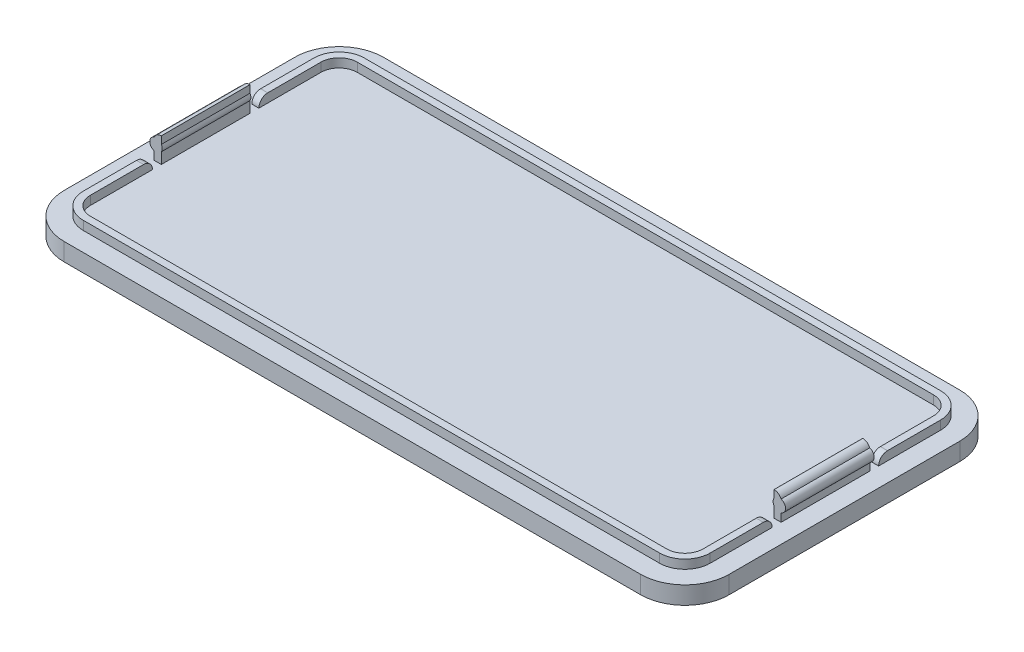
SolidWorks part; units mm, degrees
ref_plane "前视基准面" through (0, 0, 0) normal (0, 0, 1) x (1, 0, 0)
ref_plane "上视基准面" through (0, 0, 0) normal (0, 1, 0) x (1, 0, 0)
ref_plane "右视基准面" through (0, 0, 0) normal (1, 0, 0) x (0, 0, -1)
sketch "zero" plane through (0, 0, 0) normal (0, 1, 0) x (1, 0, 0)
  line L1 (-29.5, 15) -> (29.5, 15)
  line L2 (-32.5, 12) -> (-32.5, -12)
  line L3 (-29.5, -15) -> (29.5, -15)
  line L4 (32.5, 12) -> (32.5, -12)
  line L5 (-32.5, 15) -> (32.5, -15) construction
  line L6 (-32.5, -15) -> (32.5, 15) construction
  line L7 (-25.7, -15) -> (-14.5, -15)
  line L8 (-25.7, -15) -> (-25.7, -9.6569)
  line L9 (-25.7, -9.6569) -> (-14.5, -9.6569)
  line L10 (-14.5, -15) -> (-14.5, -9.6569)
  line L11 (5.2, -15) -> (12.7, -15)
  line L12 (5.2, -15) -> (5.2, -11)
  line L13 (5.2, -11) -> (12.7, -11)
  line L14 (12.7, -15) -> (12.7, -11)
  line L15 (17.8, -15) -> (25.3, -15)
  line L16 (17.8, -15) -> (17.8, -11)
  line L17 (17.8, -11) -> (25.3, -11)
  line L18 (25.3, -15) -> (25.3, -11)
  line L19 (-32.5, 7.7) -> (-19.5, 7.7)
  line L20 (-32.5, 7.7) -> (-32.5, -4.3)
  line L21 (-32.5, -4.3) -> (-19.5, -4.3)
  line L22 (-19.5, 7.7) -> (-19.5, -4.3)
  line L23 (-25.5, 14) -> (25.5, 14)
  line L24 (-25.5, 14) -> (-25.5, 8.8)
  line L25 (-25.5, 8.8) -> (25.5, 8.8)
  line L26 (25.5, 14) -> (25.5, 8.8)
  line L27 (-19.5, 7.2329) -> (-35.5, 7.2329)
  line L28 (-19.5, 7.2329) -> (-19.5, -3.7671)
  line L29 (-19.5, -3.7671) -> (-35.5, -3.7671)
  line L30 (-35.5, 7.2329) -> (-35.5, -3.7671)
  arc A0 (29.5, -15) -> (32.5, -12) centre (29.5, -12) ccw
  arc A1 (29.5, 15) -> (32.5, 12) centre (29.5, 12) cw
  arc A2 (-32.5, -12) -> (-29.5, -15) centre (-29.5, -12) ccw
  arc A3 (-29.5, 15) -> (-32.5, 12) centre (-29.5, 12) ccw
  circle A4 centre (-29, 11.4) radius 3
  circle A5 centre (-29, -11.5) radius 3
  circle A6 centre (29, 11.4) radius 3
  circle A7 centre (29, -11.5) radius 3
  circle A8 centre (-29, 11.4) radius 1.375
  circle A9 centre (-29, -11.5) radius 1.375
  circle A10 centre (29, -11.5) radius 1.375
  circle A11 centre (29, 11.4) radius 1.375
  point P0 (0, 0)
  dimension "D3" = 3
  dimension "D4" = 6
  dimension "D9" = 2.75
  dimension "D1" = 65
  dimension "D2" = 30
  dimension "D5" = 3.6
  dimension "D6" = 3.5
  dimension "D7" = 3.5
  dimension "D8" = 3.5
  dimension "D10" = 12
  dimension "D11" = 7.3
  dimension "D12" = 13
  dimension "D13" = 11.2
  dimension "D14" = 6.8
  dimension "D15" = 19.7
  dimension "D16" = 7.5
  dimension "D17" = 7.5
  dimension "D18" = 5.1
  dimension "D19" = 4
  dimension "D20" = 5.2
  dimension "D21" = 7
  dimension "D22" = 7
  dimension "D23" = 1
  dimension "D24" = 11
  dimension "D25" = 16
sketch "sugar" plane through (0, 0, 0) normal (0, 1, 0) x (1, 0, 0)
  line L1 (-29.5, 15) -> (29.5, 15)
  line L2 (-32.5, 12) -> (-32.5, -12)
  line L3 (-29.5, -15) -> (29.5, -15)
  line L4 (32.5, 12) -> (32.5, -12)
  line L5 (-32.5, 15) -> (32.5, -15) construction
  line L6 (-32.5, -15) -> (32.5, 15) construction
  line L7 (23.5, -11.5) -> (19.5, -11.5)
  line L8 (23.5, -11.5) -> (23.5, -13.9082)
  line L9 (23.5, -13.9082) -> (19.5, -13.9082)
  line L10 (19.5, -11.5) -> (19.5, -13.9082)
  line L11 (16, -11.0071) -> (8.5, -11.0071)
  line L12 (16, -11.0071) -> (16, -15)
  line L13 (16, -15) -> (8.5, -15)
  line L14 (8.5, -11.0071) -> (8.5, -15)
  line L15 (20.5, -13.9082) -> (22.5, -13.9082)
  line L16 (20.5, -13.9082) -> (20.5, -14.8173)
  line L17 (20.5, -14.8173) -> (22.5, -14.8173)
  line L18 (22.5, -13.9082) -> (22.5, -14.8173)
  arc A0 (29.5, 15) -> (32.5, 12) centre (29.5, 12) cw
  arc A1 (29.5, -15) -> (32.5, -12) centre (29.5, -12) ccw
  arc A2 (-32.5, -12) -> (-29.5, -15) centre (-29.5, -12) ccw
  arc A3 (-29.5, 15) -> (-32.5, 12) centre (-29.5, 12) ccw
  circle A4 centre (-29, 11.4) radius 3
  circle A5 centre (-29, 11.4) radius 1.375
  circle A6 centre (-29, -11.5) radius 3
  circle A7 centre (-29, -11.5) radius 1.375
  circle A8 centre (29, 11.4) radius 3
  circle A9 centre (29, 11.4) radius 1.375
  circle A10 centre (29, -11.5) radius 3
  circle A11 centre (29, -11.5) radius 1.375
  dimension "D3" = 3
  dimension "D1" = 65
  dimension "D2" = 30
  dimension "D4" = 9
  dimension "D5" = 4
  dimension "D6" = 3.5
  dimension "D7" = 7.5
  dimension "D8" = 2
  dimension "D9" = 1
sketch "case" plane through (0, 0, 0) normal (0, 1, 0) x (1, 0, 0)
  line L1 (-34.0422, 18) -> (30.9578, 18)
  line L2 (-39.0422, 13) -> (-39.0422, -13)
  line L3 (-34.0422, -18) -> (30.9578, -18)
  line L4 (35.9578, 13) -> (35.9578, -13)
  line L5 (-39.0422, 18) -> (35.9578, -18) construction
  line L6 (-39.0422, -18) -> (35.9578, 18) construction
  arc A0 (-39.0422, -13) -> (-34.0422, -18) centre (-34.0422, -13) ccw
  arc A1 (30.9578, -18) -> (35.9578, -13) centre (30.9578, -13) ccw
  arc A2 (30.9578, 18) -> (35.9578, 13) centre (30.9578, 13) cw
  arc A3 (-34.0422, 18) -> (-39.0422, 13) centre (-34.0422, 13) ccw
  point P0 (-1.5422, 0)
  point P3 (-1.5422, 0)
  dimension "D3" = 5
  dimension "D1" = 75
  dimension "D2" = 36
extrude "凸台-拉伸2" add sketch "case" along normal blind 2
sketch "草图2" plane through (0, 0, 0) normal (0, 1, 0) x (1, 0, 0)
  line L4 (-34.0422, -15.05) -> (30.9578, -15.05)
  line L5 (33.0078, -13) -> (33.0078, 13)
  line L6 (30.9578, 15.05) -> (-34.0422, 15.05)
  line L7 (-36.0922, 13) -> (-36.0922, -13)
  line L8 (33.8078, -13) -> (33.8078, 13)
  line L9 (30.9578, 15.85) -> (-34.0422, 15.85)
  line L10 (-36.8922, 13) -> (-36.8922, -13)
  line L11 (-34.0422, -15.85) -> (30.9578, -15.85)
  line L12 (33.8078, -13) -> (33.8078, 13)
  line L13 (30.9578, 15.85) -> (-34.0422, 15.85)
  line L14 (-36.8922, 13) -> (-36.8922, -13)
  line L15 (-34.0422, -15.85) -> (30.9578, -15.85)
  arc A4 (30.9578, -15.05) -> (33.0078, -13) centre (30.9578, -13) ccw
  arc A5 (33.0078, 13) -> (30.9578, 15.05) centre (30.9578, 13) ccw
  arc A6 (-34.0422, 15.05) -> (-36.0922, 13) centre (-34.0422, 13) ccw
  arc A7 (-36.0922, -13) -> (-34.0422, -15.05) centre (-34.0422, -13) ccw
  arc A8 (30.9578, -15.85) -> (33.8078, -13) centre (30.9578, -13) ccw
  arc A9 (33.8078, 13) -> (30.9578, 15.85) centre (30.9578, 13) ccw
  arc A10 (-34.0422, 15.85) -> (-36.8922, 13) centre (-34.0422, 13) ccw
  arc A11 (-36.8922, -13) -> (-34.0422, -15.85) centre (-34.0422, -13) ccw
  arc A12 (30.9578, -15.85) -> (33.8078, -13) centre (30.9578, -13) ccw
  arc A13 (33.8078, 13) -> (30.9578, 15.85) centre (30.9578, 13) ccw
  arc A14 (-34.0422, 15.85) -> (-36.8922, 13) centre (-34.0422, 13) ccw
  arc A15 (-36.8922, -13) -> (-34.0422, -15.85) centre (-34.0422, -13) ccw
  dimension "D1" = 2.15
  dimension "D2" = 0.8
ref_plane "基准面1" through (0, 2, 0) normal (0, 1, 0) x (1, 0, 0)
sketch "草图3" plane through (0, 2, 0) normal (0, 1, 0) x (1, 0, 0)
  line L4 (-34.0422, -15.05) -> (30.9578, -15.05)
  line L5 (33.0078, -13) -> (33.0078, 13)
  line L6 (30.9578, 15.05) -> (-34.0422, 15.05)
  line L7 (-36.0922, 13) -> (-36.0922, -13)
  line L8 (-34.0422, -15.05) -> (30.9578, -15.05)
  line L9 (33.0078, -13) -> (33.0078, 13)
  line L10 (30.9578, 15.05) -> (-34.0422, 15.05)
  line L11 (-36.0922, 13) -> (-36.0922, -13)
  line L12 (-36.8922, 13) -> (-36.8922, -13)
  line L13 (-34.0422, -15.85) -> (30.9578, -15.85)
  line L14 (33.8078, -13) -> (33.8078, 13)
  line L15 (30.9578, 15.85) -> (-34.0422, 15.85)
  line L16 (-36.8922, 13) -> (-36.8922, -13)
  line L17 (-34.0422, -15.85) -> (30.9578, -15.85)
  line L18 (33.8078, -13) -> (33.8078, 13)
  line L19 (30.9578, 15.85) -> (-34.0422, 15.85)
  arc A4 (30.9578, -15.05) -> (33.0078, -13) centre (30.9578, -13) ccw
  arc A5 (33.0078, 13) -> (30.9578, 15.05) centre (30.9578, 13) ccw
  arc A6 (-34.0422, 15.05) -> (-36.0922, 13) centre (-34.0422, 13) ccw
  arc A7 (-36.0922, -13) -> (-34.0422, -15.05) centre (-34.0422, -13) ccw
  arc A8 (30.9578, -15.05) -> (33.0078, -13) centre (30.9578, -13) ccw
  arc A9 (33.0078, 13) -> (30.9578, 15.05) centre (30.9578, 13) ccw
  arc A10 (-34.0422, 15.05) -> (-36.0922, 13) centre (-34.0422, 13) ccw
  arc A11 (-36.0922, -13) -> (-34.0422, -15.05) centre (-34.0422, -13) ccw
  arc A12 (-36.8922, -13) -> (-34.0422, -15.85) centre (-34.0422, -13) ccw
  arc A13 (30.9578, -15.85) -> (33.8078, -13) centre (30.9578, -13) ccw
  arc A14 (33.8078, 13) -> (30.9578, 15.85) centre (30.9578, 13) ccw
  arc A15 (-34.0422, 15.85) -> (-36.8922, 13) centre (-34.0422, 13) ccw
  arc A16 (-36.8922, -13) -> (-34.0422, -15.85) centre (-34.0422, -13) ccw
  arc A17 (30.9578, -15.85) -> (33.8078, -13) centre (30.9578, -13) ccw
  arc A18 (33.8078, 13) -> (30.9578, 15.85) centre (30.9578, 13) ccw
  arc A19 (-34.0422, 15.85) -> (-36.8922, 13) centre (-34.0422, 13) ccw
  dimension "D1" = 0
  dimension "D2" = 0
extrude "凸台-拉伸4" add sketch "草图3" along normal blind 1
ref_plane "基准面3" through (33.8078, 0, 0) normal (1, 0, 0) x (0, 0, -1)
sketch "草图7" plane through (0, 2, 0) normal (0, 1, 0) x (1, 0, 0)
  line L0 (-36.8922, 13) -> (-36.8922, -13) construction
  line L1 (-36.8922, 5) -> (-36.0922, 5)
  line L2 (-36.8922, 5) -> (-36.8922, -5)
  line L3 (-36.8922, -5) -> (-36.0922, -5)
  line L4 (-36.0922, 5) -> (-36.0922, -5)
  line L5 (-36.0922, 13) -> (-36.0922, -13) construction
  point P10 (-36.0922, 0)
  dimension "D1" = 5
  dimension "D2" = 10
extrude "凸台-拉伸8" add sketch "草图7" along normal blind 2.8
ref_plane "基准面5" through (0, 0, 5) normal (0, 0, 1) x (1, 0, 0)
sketch "草图8" plane through (0, 0, 5) normal (0, 0, 1) x (1, 0, 0)
  line L0 (-34.0422, 2) -> (-39.0422, 2) construction
  line L1 (-36.8922, 4.8) -> (-36.8922, 3) construction
  circle A0 centre (-36.6922, 3.6) radius 0.7
  dimension "D1" = 1.4
  dimension "D2" = 1.6
  dimension "D3" = 0.2
extrude "凸台-拉伸9" add sketch "草图8" against normal blind 10
fillet "圆角1" radius 0.85 1 edges at (-36.8922, 4.8, 0)
ref_plane "基准面7" through (-36.8922, 0, 0) normal (-1, 0, 0) x (0, 0, 1)
sketch "草图11" plane through (-36.8922, 0, 0) normal (-1, 0, 0) x (0, 0, 1)
  line L0 (-13, 2) -> (13, 2) construction
  line L1 (5, 3) -> (6, 3)
  line L2 (5, 3) -> (5, 2)
  line L3 (5, 2) -> (6, 2)
  line L4 (6, 3) -> (6, 2)
  line L6 (-5, 3) -> (-6, 3)
  line L7 (-5, 3) -> (-5, 2)
  line L8 (-5, 2) -> (-6, 2)
  line L9 (-6, 3) -> (-6, 2)
  dimension "D1" = 1
  dimension "D2" = 1
extrude "切除-拉伸1" cut sketch "草图11" against normal blind 1.2
fillet "圆角2" radius 1 2 edges at (-36.4922, 3, 6) (-36.4922, 3, -6)
ref_plane "基准面8" through (0, 0, 0) normal (0, -1, 0) x (-1, 0, 0)
sketch "草图12" plane through (0, 0, 0) normal (0, -1, 0) x (-1, 0, 0)
  line L76 (34.0422, -18) -> (-30.9578, -18) construction
  line L78 (39.0422, 13) -> (39.0422, -13) construction
  line B0 (-8.1993, 5.026) -> (-9.0198, 5.499)
  line B1 (-9.0198, 5.499) -> (-13.2767, 7.9551)
  line B2 (-13.2767, 7.9551) -> (-14.0973, 8.4339)
  line B3 (-15.8183, 8.4339) -> (-16.6389, 7.9551)
  line B4 (-16.6389, 7.9551) -> (-20.8958, 5.499)
  line B5 (-20.8958, 5.499) -> (-21.7165, 5.026)
  line B6 (-22.577, 3.5387) -> (-22.577, -3.2769)
  line B7 (-21.7165, -4.7643) -> (-20.8958, -5.2373)
  line B8 (-20.8958, -5.2373) -> (-16.6389, -7.6934)
  line B9 (-16.6389, -7.6934) -> (-15.8183, -8.172)
  line B10 (-14.0973, -8.172) -> (-13.2767, -7.6934)
  line B11 (-13.2767, -7.6934) -> (-9.0198, -5.2373)
  line B12 (-9.0198, -5.2373) -> (-8.1993, -4.7643)
  line B13 (-7.3388, -3.2769) -> (-7.3388, 3.5387)
  line B14 (-20.6223, 4.3479) -> (-15.3568, 7.391)
  line B15 (-14.5532, 7.391) -> (-9.3162, 4.3422)
  line B16 (-9.3105, 3.6413) -> (-14.3993, 0.5982)
  line B17 (-12.8208, -4.5591) -> (-13.4135, -4.8896)
  line B18 (-13.4705, -4.9865) -> (-13.4705, -6.6961)
  line B19 (-13.5274, -6.793) -> (-14.633, -7.4198)
  line B20 (-14.7983, -7.3229) -> (-14.7983, -2.046)
  line B21 (-14.7413, -1.9491) -> (-12.8607, -0.8835)
  line B22 (-8.9173, -4.2058) -> (-10.0114, -4.8269)
  line B23 (-10.1767, -4.7301) -> (-10.1767, -2.2169)
  line B24 (-10.1197, -2.1201) -> (-9.0256, -1.5046)
  line B25 (-8.8603, -1.6015) -> (-8.8603, -4.1089)
  line B26 (-12.8893, -3.5447) -> (-13.4135, -3.8069)
  line B27 (-13.4705, -3.6872) -> (-13.4705, -2.3423)
  line B28 (-13.4135, -2.2455) -> (-12.9234, -1.9719)
  line B29 (-3.344, 3.06) -> (-5.2189, 3.06)
  line B30 (-5.2189, 3.06) -> (-5.2189, -3.5048)
  line B31 (-5.2189, -3.5048) -> (-4.3868, -3.5048)
  line B32 (-4.3868, -3.5048) -> (-4.3868, -0.9005)
  line B33 (-4.3868, -0.9005) -> (-3.2984, -0.9005)
  line B34 (-3.4066, -0.2281) -> (-4.3868, -0.2281)
  line B35 (-4.3868, -0.2281) -> (-4.3868, 2.3876)
  line B36 (-4.3868, 2.3876) -> (-3.4408, 2.3876)
  line B37 (0.1948, 1.3618) -> (0.1948, -3.5048)
  line B38 (0.1948, -3.5048) -> (1.0098, -3.5048)
  line B39 (1.0098, -3.5048) -> (1.0098, 1.3618)
  line B40 (1.0098, 1.3618) -> (0.1948, 1.3618)
  line B41 (5.7169, 0.2847) -> (4.8849, 0.6153)
  line B42 (6.0417, 1.4017) -> (6.8396, 2.4047)
  line B43 (3.6084, -0.5586) -> (4.4575, -0.9177)
  line B44 (2.9074, -1.5673) -> (2.0014, -2.6729)
  line B45 (10.8229, 1.5898) -> (10.8229, -1.7497)
  line B46 (9.3811, -1.3621) -> (9.3811, 1.5898)
  line B47 (9.3811, 1.5898) -> (7.7912, 1.5898)
  line B48 (7.7912, 1.5898) -> (7.7912, -1.5616)
  line B49 (10.9711, -2.8039) -> (11.0052, -2.8039)
  line B50 (11.0052, -2.8039) -> (11.1193, -3.5048)
  line B51 (11.1193, -3.5048) -> (12.4185, -3.5048)
  line B52 (12.4185, -3.5048) -> (12.4185, 1.5898)
  line B53 (12.4185, 1.5898) -> (10.8229, 1.5898)
  line B54 (16.2708, -2.5019) -> (15.4673, -2.5019)
  line B55 (17.365, 0.4386) -> (18.1513, 0.4386)
  line B56 (18.1513, 0.4386) -> (18.1513, 1.5898)
  line B57 (18.1513, 1.5898) -> (16.2822, 1.5898)
  line B58 (14.0312, -1.4533) -> (14.0312, -1.4875)
  line B59 (13.9344, -3.3168) -> (13.9344, -3.3624)
  line B60 (15.4844, -3.7214) -> (15.9688, -3.7214)
  line B61 (18.6072, 1.0484) -> (19.1657, -0.0002)
  line B62 (21.411, -2.992) -> (21.4508, -2.992)
  line B63 (21.4508, -2.992) -> (21.5648, -3.5048)
  line B64 (21.5648, -3.5048) -> (22.8641, -3.5048)
  line B65 (22.8641, -3.5048) -> (22.8641, -0.6099)
  line B66 (21.2685, -1.1741) -> (21.2685, -1.989)
  line B67 (25.3545, 0.7065) -> (25.3203, 0.7065)
  line B68 (25.3203, 0.7065) -> (25.212, 1.5898)
  line B69 (25.212, 1.5898) -> (23.9127, 1.5898)
  line B70 (23.9127, 1.5898) -> (23.9127, -3.5048)
  line B71 (23.9127, -3.5048) -> (25.4969, -3.5048)
  line B72 (25.4969, -3.5048) -> (25.4969, -0.5928)
  line B73 (27.1552, 0.2392) -> (27.423, 1.6125)
  line B74 (-13.4135, -3.8069) -> (-13.4135, -4.8896)
  line B75 (-13.4705, -3.6872) -> (-13.4705, -4.9865)
  spline B76 degree 3 poles (-14.0973, 8.4339) (-14.3652, 8.582) (-14.6615, 8.6618) (-14.9578, 8.6618) knots 3 3 3 3 4 4 4 4
  spline B77 degree 3 poles (-14.9578, 8.6618) (-15.2541, 8.6618) (-15.5505, 8.582) (-15.8183, 8.4339) knots 4 4 4 4 5 5 5 5
  spline B78 degree 3 poles (-21.7165, 5.026) (-22.2464, 4.7183) (-22.577, 4.1485) (-22.577, 3.5387) knots 8 8 8 8 9 9 9 9
  spline B79 degree 3 poles (-22.577, -3.2769) (-22.577, -3.8923) (-22.2464, -4.4565) (-21.7165, -4.7643) knots 10 10 10 10 11 11 11 11
  spline B80 degree 3 poles (-15.8183, -8.172) (-15.5505, -8.3259) (-15.2541, -8.4) (-14.9578, -8.4) knots 14 14 14 14 15 15 15 15
  spline B81 degree 3 poles (-14.9578, -8.4) (-14.6615, -8.4) (-14.3652, -8.3259) (-14.0973, -8.172) knots 15 15 15 15 16 16 16 16
  spline B82 degree 3 poles (-8.1993, -4.7643) (-7.6636, -4.4565) (-7.3388, -3.8923) (-7.3388, -3.2769) knots 19 19 19 19 20 20 20 20
  spline B83 degree 3 poles (-7.3388, 3.5387) (-7.3388, 4.1485) (-7.6636, 4.7183) (-8.1993, 5.026) knots 21 21 21 21 22 22 22 22
  spline B84 degree 2 poles (-15.5106, 0.5982) (-20.6622, 3.5729) (-20.6736, 3.5786) knots 0 0 0 1 1 1
  spline B85 degree 3 poles (-20.6736, 3.5786) (-20.9414, 3.7723) (-20.9129, 4.1826) (-20.6223, 4.3479) knots 1 1 1 1 2 2 2 2
  spline B86 degree 3 poles (-15.3568, 7.391) (-15.1117, 7.5335) (-14.8039, 7.5335) (-14.5532, 7.391) knots 3 3 3 3 4 4 4 4
  spline B87 degree 3 poles (-9.3162, 4.3422) (-9.0484, 4.1883) (-9.0427, 3.8008) (-9.3105, 3.6413) knots 5 5 5 5 6 6 6 6
  spline B88 degree 3 poles (-14.3993, 0.5982) (-14.7413, 0.3987) (-15.1687, 0.3987) (-15.5106, 0.5982) knots 7 7 7 7 8 8 8 8
  spline B89 degree 3 poles (-13.4705, -6.6961) (-13.4705, -6.736) (-13.4876, -6.7702) (-13.5274, -6.793) knots 3 3 3 3 4 4 4 4
  spline B90 degree 3 poles (-14.633, -7.4198) (-14.7071, -7.4597) (-14.7983, -7.4084) (-14.7983, -7.3229) knots 5 5 5 5 6 6 6 6
  spline B91 degree 3 poles (-14.7983, -2.046) (-14.7983, -2.0061) (-14.7812, -1.9662) (-14.7413, -1.9491) knots 7 7 7 7 8 8 8 8
  spline B92 degree 3 poles (-12.8607, -0.8835) (-11.6412, -0.1939) (-10.6326, -0.0572) (-10.6326, -1.4249) knots 9 9 9 9 10 10 10 10
  spline B93 degree 3 poles (-10.6326, -1.4249) (-10.6326, -2.7412) (-11.6526, -3.898) (-12.8208, -4.5591) knots 10 10 10 10 11 11 11 11
  spline B94 degree 3 poles (-8.8603, -4.1089) (-8.8603, -4.1488) (-8.8831, -4.1887) (-8.9173, -4.2058) knots 0 0 0 0 1 1 1 1
  spline B95 degree 3 poles (-10.0114, -4.8269) (-10.0855, -4.8668) (-10.1767, -4.8155) (-10.1767, -4.7301) knots 2 2 2 2 3 3 3 3
  spline B96 degree 3 poles (-10.1767, -2.2169) (-10.1767, -2.1771) (-10.1539, -2.1429) (-10.1197, -2.1201) knots 4 4 4 4 5 5 5 5
  spline B97 degree 3 poles (-9.0256, -1.5046) (-8.9515, -1.4647) (-8.8603, -1.516) (-8.8603, -1.6015) knots 6 6 6 6 7 7 7 7
  spline B98 degree 3 poles (-9.5156, 0.1651) (-9.0768, 0.4158) (-8.7634, 0.3076) (-8.7634, -0.0914) (-8.7634, -0.4846) (-9.0768, -0.9461) (-9.5156, -1.1912) knots 2 2 2 2 3 3 3 4 4 4 4
  spline B99 degree 3 poles (-9.5156, -1.1912) (-9.9601, -1.4476) (-10.2735, -1.3394) (-10.2735, -0.9461) (-10.2735, -0.5415) (-9.9601, -0.0856) (-9.5156, 0.1651) knots 0 0 0 0 1 1 1 2 2 2 2
  spline B100 degree 3 poles (-11.9319, -2.16) (-11.9319, -2.7013) (-12.2395, -3.18) (-12.8893, -3.5447) knots 0 0 0 0 1 1 1 1
  spline B101 degree 3 poles (-13.4705, -2.3423) (-13.4705, -2.3024) (-13.4477, -2.2625) (-13.4135, -2.2455) knots 4 4 4 4 5 5 5 5
  spline B102 degree 3 poles (-12.9234, -1.9719) (-12.2852, -1.6072) (-11.9319, -1.6015) (-11.9319, -2.16) knots 6 6 6 6 7 7 7 7
  spline B103 degree 3 poles (-3.2984, -0.9005) (-1.868, -0.9005) (-0.8822, -0.2509) (-0.8822, 1.1339) knots 5 5 5 5 6 6 6 6
  spline B104 degree 3 poles (-0.8822, 1.1339) (-0.8822, 2.5699) (-1.868, 3.06) (-3.344, 3.06) knots 6 6 6 6 7 7 7 7
  spline B105 degree 3 poles (-3.4408, 2.3876) (-2.2897, 2.3876) (-1.7084, 2.0855) (-1.7084, 1.1339) knots 3 3 3 3 4 4 4 4
  spline B106 degree 3 poles (-1.7084, 1.1339) (-1.7084, 0.1936) (-2.2498, -0.2281) (-3.4066, -0.2281) knots 4 4 4 4 5 5 5 5
  spline B107 degree 3 poles (0.6052, 2.3648) (0.93, 2.3648) (1.1694, 2.587) (1.1694, 2.889) (1.1694, 3.2253) (0.93, 3.419) (0.6052, 3.419) knots 2 2 2 2 3 3 3 4 4 4 4
  spline B108 degree 3 poles (0.6052, 3.419) (0.2804, 3.419) (0.041, 3.2253) (0.041, 2.889) (0.041, 2.587) (0.2804, 2.3648) (0.6052, 2.3648) knots 0 0 0 0 1 1 1 2 2 2 2
  spline B109 degree 3 poles (4.8849, 0.6153) (4.2979, 0.8489) (3.8762, 0.9914) (3.8762, 1.3618) knots 1 1 1 1 2 2 2 2
  spline B110 degree 3 poles (3.8762, 1.3618) (3.8762, 1.7151) (4.1783, 1.9146) (4.674, 1.9146) knots 2 2 2 2 3 3 3 3
  spline B111 degree 3 poles (4.674, 1.9146) (5.1926, 1.9146) (5.6029, 1.7379) (6.0417, 1.4017) knots 3 3 3 3 4 4 4 4
  spline B112 degree 3 poles (6.8396, 2.4047) (6.2583, 2.9916) (5.4433, 3.2879) (4.674, 3.2879) knots 5 5 5 5 6 6 6 6
  spline B113 degree 3 poles (4.674, 3.2879) (3.2551, 3.2879) (2.2521, 2.3876) (2.2521, 1.2706) knots 6 6 6 6 7 7 7 7
  spline B114 degree 3 poles (2.2521, 1.2706) (2.2521, 0.3019) (2.9074, -0.2794) (3.6084, -0.5586) knots 7 7 7 7 8 8 8 8
  spline B115 degree 3 poles (4.4575, -0.9177) (5.0274, -1.157) (5.3978, -1.2824) (5.3978, -1.6699) knots 9 9 9 9 10 10 10 10
  spline B116 degree 3 poles (5.3978, -1.6699) (5.3978, -2.0289) (5.1185, -2.2511) (4.5259, -2.2511) knots 10 10 10 10 11 11 11 11
  spline B117 degree 3 poles (4.5259, -2.2511) (4.0016, -2.2511) (3.3804, -1.9719) (2.9074, -1.5673) knots 11 11 11 11 12 12 12 12
  spline B118 degree 3 poles (2.0014, -2.6729) (2.6909, -3.3054) (3.6254, -3.6302) (4.4916, -3.6302) knots 13 13 13 13 14 14 14 14
  spline B119 degree 3 poles (4.4916, -3.6302) (6.1044, -3.6302) (7.0389, -2.6557) (7.0389, -1.5445) knots 14 14 14 14 15 15 15 15
  spline B120 degree 3 poles (7.0389, -1.5445) (7.0389, -0.6042) (6.5432, -0.0458) (5.7169, 0.2847) knots 15 15 15 15 16 16 16 16
  spline B121 degree 3 poles (10.8229, -1.7497) (10.5551, -2.1258) (10.3328, -2.2682) (9.9738, -2.2682) knots 1 1 1 1 2 2 2 2
  spline B122 degree 3 poles (9.9738, -2.2682) (9.5692, -2.2682) (9.3811, -2.0688) (9.3811, -1.3621) knots 2 2 2 2 3 3 3 3
  spline B123 degree 3 poles (7.7912, -1.5616) (7.7912, -2.8324) (8.2642, -3.6302) (9.3754, -3.6302) knots 6 6 6 6 7 7 7 7
  spline B124 degree 3 poles (9.3754, -3.6302) (10.0706, -3.6302) (10.5494, -3.3054) (10.9711, -2.8039) knots 7 7 7 7 8 8 8 8
  spline B125 degree 3 poles (15.4673, -2.5019) (14.9202, -2.5019) (14.7151, -2.3936) (14.7151, -2.16) knots 1 1 1 1 2 2 2 2
  spline B126 degree 3 poles (14.7151, -2.16) (14.7151, -1.989) (14.7549, -1.9092) (14.8746, -1.8009) knots 2 2 2 2 3 3 3 3
  spline B127 degree 3 poles (14.8746, -1.8009) (15.0969, -1.8636) (15.302, -1.8921) (15.473, -1.8921) knots 3 3 3 3 4 4 4 4
  spline B128 degree 3 poles (15.473, -1.8921) (16.6013, -1.8921) (17.5074, -1.3735) (17.5074, -0.1825) knots 4 4 4 4 5 5 5 5
  spline B129 degree 3 poles (17.5074, -0.1825) (17.5074, 0.0625) (17.4447, 0.2962) (17.365, 0.4386) knots 5 5 5 5 6 6 6 6
  spline B130 degree 3 poles (16.2822, 1.5898) (16.0485, 1.6752) (15.7693, 1.7151) (15.473, 1.7151) knots 9 9 9 9 10 10 10 10
  spline B131 degree 3 poles (15.473, 1.7151) (14.3732, 1.7151) (13.3417, 1.1111) (13.3417, -0.1369) knots 10 10 10 10 11 11 11 11
  spline B132 degree 3 poles (13.3417, -0.1369) (13.3417, -0.7296) (13.6722, -1.2026) (14.0312, -1.4533) knots 11 11 11 11 12 12 12 12
  spline B133 degree 3 poles (14.0312, -1.4875) (13.7007, -1.7212) (13.467, -2.0802) (13.467, -2.4392) knots 13 13 13 13 14 14 14 14
  spline B134 degree 3 poles (13.467, -2.4392) (13.467, -2.8666) (13.6665, -3.1344) (13.9344, -3.3168) knots 14 14 14 14 15 15 15 15
  spline B135 degree 3 poles (13.9344, -3.3624) (13.4613, -3.6017) (13.2106, -3.9436) (13.2106, -4.3653) knots 16 16 16 16 17 17 17 17
  spline B136 degree 3 poles (13.2106, -4.3653) (13.2106, -5.2771) (14.1737, -5.6475) (15.3476, -5.6475) knots 17 17 17 17 18 18 18 18
  spline B137 degree 3 poles (15.3476, -5.6475) (17.1199, -5.6475) (18.2312, -4.8839) (18.2312, -3.8069) knots 18 18 18 18 19 19 19 19
  spline B138 degree 3 poles (18.2312, -3.8069) (18.2312, -2.8837) (17.5245, -2.5019) (16.2708, -2.5019) knots 19 19 19 19 20 20 20 20
  spline B139 degree 3 poles (15.473, -0.9347) (15.1083, -0.9347) (14.8291, -0.6669) (14.8291, -0.1369) (14.8291, 0.3816) (15.1083, 0.6495) (15.473, 0.6495) knots 2 2 2 2 3 3 3 4 4 4 4
  spline B140 degree 3 poles (15.473, 0.6495) (15.8491, 0.6495) (16.1169, 0.3816) (16.1169, -0.1369) (16.1169, -0.6669) (15.8491, -0.9347) (15.473, -0.9347) knots 0 0 0 0 1 1 1 2 2 2 2
  spline B141 degree 3 poles (15.5983, -4.6503) (14.943, -4.6503) (14.5156, -4.4736) (14.5156, -4.1146) knots 0 0 0 0 1 1 1 1
  spline B142 degree 3 poles (14.5156, -4.1146) (14.5156, -3.9436) (14.5953, -3.8012) (14.7549, -3.6587) knots 1 1 1 1 2 2 2 2
  spline B143 degree 3 poles (14.7549, -3.6587) (14.9202, -3.7043) (15.114, -3.7214) (15.4844, -3.7214) knots 2 2 2 2 3 3 3 3
  spline B144 degree 3 poles (15.9688, -3.7214) (16.4417, -3.7214) (16.7096, -3.7841) (16.7096, -4.0861) knots 4 4 4 4 5 5 5 5
  spline B145 degree 3 poles (16.7096, -4.0861) (16.7096, -4.4109) (16.2537, -4.6503) (15.5983, -4.6503) knots 5 5 5 5 6 6 6 6
  spline B146 degree 3 poles (20.8013, 1.7151) (20.0091, 1.7151) (19.2797, 1.4473) (18.6072, 1.0484) knots 0 0 0 0 1 1 1 1
  spline B147 degree 3 poles (19.1657, -0.0002) (19.6729, 0.2847) (20.0946, 0.4443) (20.4992, 0.4443) knots 2 2 2 2 3 3 3 3
  spline B148 degree 3 poles (20.4992, 0.4443) (21.0177, 0.4443) (21.2344, 0.205) (21.2685, -0.2053) knots 3 3 3 3 4 4 4 4
  spline B149 degree 3 poles (21.2685, -0.2053) (19.2797, -0.4219) (18.4362, -1.0031) (18.4362, -2.0802) knots 4 4 4 4 5 5 5 5
  spline B150 degree 3 poles (18.4362, -2.0802) (18.4362, -2.9293) (19.0118, -3.6302) (19.9522, -3.6302) knots 5 5 5 5 6 6 6 6
  spline B151 degree 3 poles (19.9522, -3.6302) (20.5163, -3.6302) (20.9893, -3.3681) (21.411, -2.992) knots 6 6 6 6 7 7 7 7
  spline B152 degree 3 poles (22.8641, -0.6099) (22.8641, 0.9857) (22.1176, 1.7151) (20.8013, 1.7151) knots 11 11 11 11 12 12 12 12
  spline B153 degree 3 poles (21.2685, -1.989) (21.0349, -2.2398) (20.824, -2.3936) (20.4992, -2.3936) knots 0 0 0 0 1 1 1 1
  spline B154 degree 3 poles (20.4992, -2.3936) (20.1686, -2.3936) (19.9522, -2.2511) (19.9522, -1.9548) knots 1 1 1 1 2 2 2 2
  spline B155 degree 3 poles (19.9522, -1.9548) (19.9522, -1.5958) (20.277, -1.3109) (21.2685, -1.1741) knots 2 2 2 2 3 3 3 3
  spline B156 degree 3 poles (26.8076, 1.7151) (26.2947, 1.7151) (25.7305, 1.3846) (25.3545, 0.7065) knots 0 0 0 0 1 1 1 1
  spline B157 degree 3 poles (25.4969, -0.5928) (25.7648, 0.0796) (26.2207, 0.3189) (26.5967, 0.3189) knots 7 7 7 7 8 8 8 8
  spline B158 degree 3 poles (26.5967, 0.3189) (26.8247, 0.3189) (26.9729, 0.2847) (27.1552, 0.2392) knots 8 8 8 8 9 9 9 9
  spline B159 degree 3 poles (27.423, 1.6125) (27.2806, 1.6752) (27.1096, 1.7151) (26.8076, 1.7151) knots 10 10 10 10 11 11 11 11
  dimension "D1" = 9.6
  dimension "D2" = 54
sketch_block_instance "块1-1"
sketch_block "块1"
extrude "切除-拉伸2" cut sketch "草图12" against normal blind 0.5
sketch "草图13" plane through (0, 3, 0) normal (0, 1, 0) x (1, 0, 0)
  line L0 (33.0078, -13) -> (33.0078, 13) construction
  line L1 (33.0078, 5) -> (33.8078, 5)
  line L2 (33.0078, 5) -> (33.0078, -5)
  line L3 (33.0078, -5) -> (33.8078, -5)
  line L4 (33.8078, 5) -> (33.8078, -5)
  line L5 (33.8078, -13) -> (33.8078, 13) construction
  line L7 (35.9578, -13) -> (35.9578, 13) construction
  point P12 (35.9578, 0)
  point P13 (33.8078, 0)
  dimension "D1" = 10
extrude "凸台-拉伸10" add sketch "草图13" along normal blind 1.8
sketch "草图14" plane through (0, 0, 5) normal (0, 0, 1) x (1, 0, 0)
  line L0 (33.8078, 2) -> (30.9578, 2) construction
  line L1 (33.8078, 4.8) -> (33.8078, 3) construction
  circle A0 centre (33.6078, 3.6) radius 0.7
  dimension "D2" = 1.4
  dimension "D1" = 1.6
  dimension "D3" = 0.2
extrude "凸台-拉伸11" add sketch "草图14" against normal blind 10
fillet "圆角3" radius 0.85 1 edges at (33.8078, 4.8, 0)
sketch "草图15" plane through (0, 3, 0) normal (0, 1, 0) x (1, 0, 0)
  line L0 (33.8078, 5) -> (33.8078, 13) construction
  line L1 (33.0078, 5) -> (33.8078, 5)
  line L2 (33.0078, 5) -> (33.0078, 6)
  line L3 (33.0078, 6) -> (33.8078, 6)
  line L4 (33.8078, 5) -> (33.8078, 6)
  line L5 (33.8078, -13) -> (33.8078, -5) construction
  line L6 (33.0078, -5) -> (33.8078, -5)
  line L7 (33.0078, -5) -> (33.0078, -6)
  line L8 (33.0078, -6) -> (33.8078, -6)
  line L9 (33.8078, -5) -> (33.8078, -6)
  dimension "D1" = 1
  dimension "D2" = 1
extrude "切除-拉伸3" cut sketch "草图15" against normal blind 1
fillet "圆角4" radius 1 2 edges at (33.4078, 3, 6) (33.4078, 3, -6)
